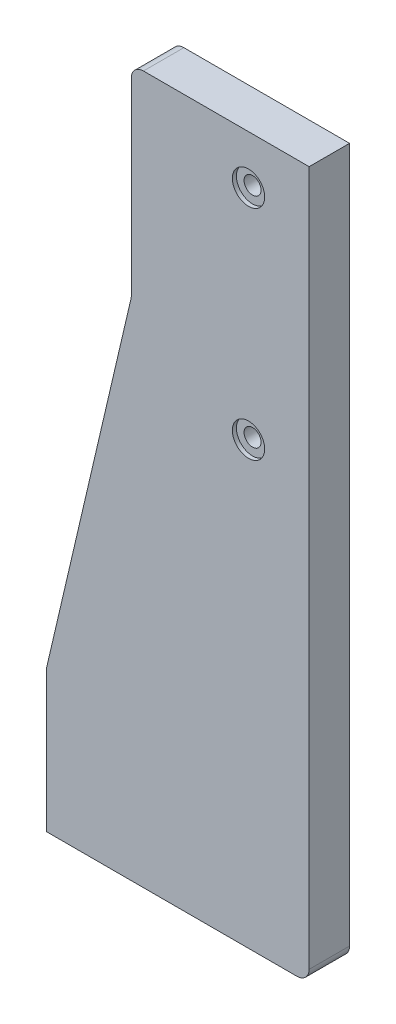
SolidWorks part; units mm, degrees
ref_plane "前视基准面" through (0, 0, 0) normal (0, 0, 1) x (1, 0, 0)
ref_plane "上视基准面" through (0, 0, 0) normal (0, 1, 0) x (1, 0, 0)
ref_plane "右视基准面" through (0, 0, 0) normal (1, 0, 0) x (0, 0, -1)
sketch "草图10" plane through (0, 0, 0) normal (0, 0, 1) x (1, 0, 0)
  line L0 (0, 0) -> (65, 0)
  line L1 (65, 0) -> (65, 175)
  line L2 (65, 175) -> (21, 175)
  line L3 (21, 175) -> (21, 125)
  line L4 (21, 125) -> (0, 35)
  line L5 (0, 35) -> (0, 0)
  line L6 (69.8985, 175) -> (69.8985, 0) construction
  dimension "D1" = 65
  dimension "D2" = 175
  dimension "D3" = 44
  dimension "D4" = 50
  dimension "D5" = 35
extrude "凸台-拉伸4" add sketch "草图10" along normal blind 10 contours L4 L5 L0 L1 L2 L3
sketch "草图11" plane through (0, 0, 10) normal (0, 0, 1) x (1, 0, 0)
  line L0 (50, 175) -> (50, 0) construction
  line L1 (65, 175) -> (21, 175) construction
  line L2 (0, 0) -> (65, 0) construction
  line L3 (65, 0) -> (65, 175) construction
  circle A0 centre (50, 163) radius 2.1
  circle A1 centre (50, 109) radius 2.1
  dimension "D1" = 4.2
  dimension "D2" = 12
  dimension "D3" = 54
  dimension "D4" = 15
extrude "切除-拉伸8" cut sketch "草图11" against normal through all contours A1 | A0
sketch "草图12" plane through (0, 0, 10) normal (0, 0, 1) x (1, 0, 0)
  circle A0 centre (50, 163) radius 4
  circle A1 centre (50, 109) radius 4
  dimension "D1" = 8
extrude "切除-拉伸9" cut sketch "草图12" against normal blind 1
fillet "圆角7" radius 3 3 edges at (65, 0, 5) (21, 125, 5) (21, 175, 5)
